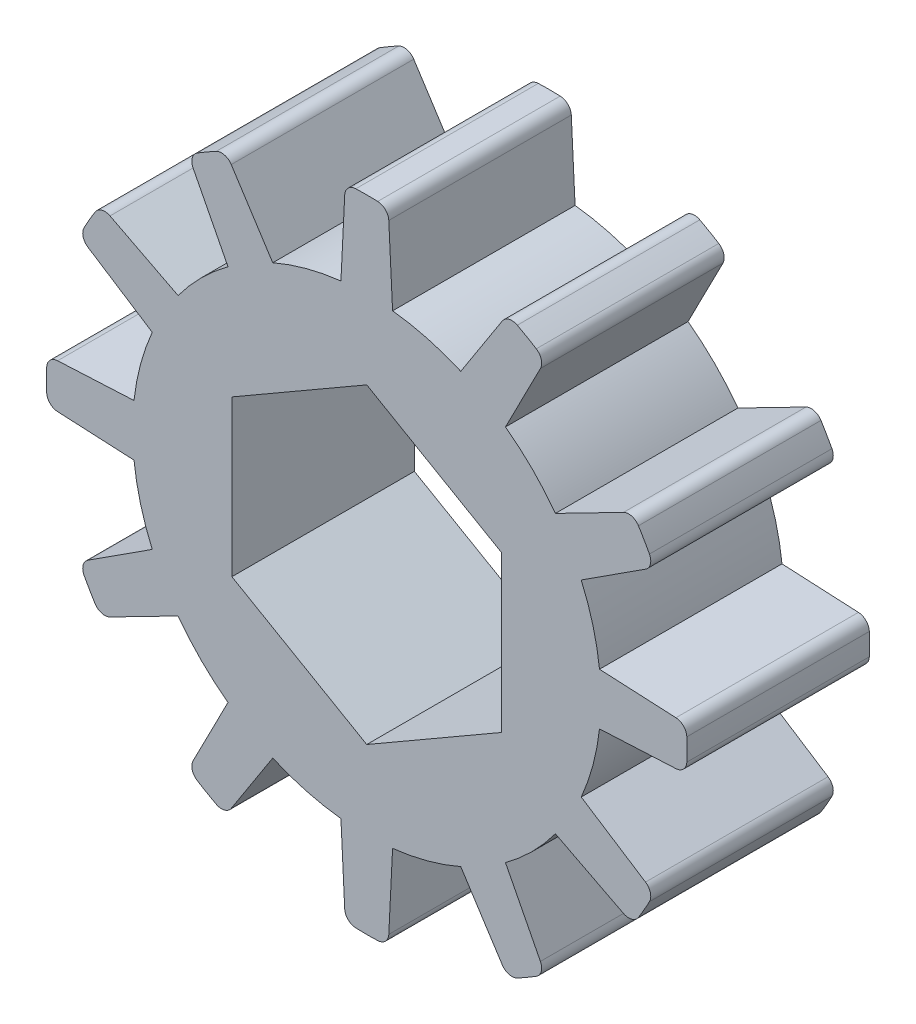
SolidWorks part; units mm, degrees
material "ABS"
ref_plane "Alzado" through (0, 0, 0) normal (0, 0, 1) x (1, 0, 0)
ref_plane "Planta" through (0, 0, 0) normal (0, 1, 0) x (1, 0, 0)
ref_plane "Vista lateral" through (0, 0, 0) normal (1, 0, 0) x (0, 0, -1)
sketch "Croquis1" plane through (0, 0, 0) normal (0, 0, 1) x (1, 0, 0)
  line L0 (0, 0) -> (0, 4.6049) construction
  line L1 (0.375, 5.5679) -> (0.45, 4.0556)
  line L2 (-0.375, 5.5679) -> (-0.45, 4.0556)
  line L3 (2.4592, 5.0094) -> (1.6381, 3.7373)
  line L4 (3.1087, 4.6344) -> (2.4175, 3.2873)
  line L5 (4.6344, 3.1087) -> (3.2873, 2.4175)
  line L6 (5.0094, 2.4592) -> (3.7373, 1.6381)
  line L7 (5.5679, 0.375) -> (4.0556, 0.45)
  line L8 (5.5679, -0.375) -> (4.0556, -0.45)
  line L9 (5.0094, -2.4592) -> (3.7373, -1.6381)
  line L10 (4.6344, -3.1087) -> (3.2873, -2.4175)
  line L11 (3.1087, -4.6344) -> (2.4175, -3.2873)
  line L12 (2.4592, -5.0094) -> (1.6381, -3.7373)
  line L13 (0.375, -5.5679) -> (0.45, -4.0556)
  line L14 (-0.375, -5.5679) -> (-0.45, -4.0556)
  line L15 (-2.4592, -5.0094) -> (-1.6381, -3.7373)
  line L16 (-3.1087, -4.6344) -> (-2.4175, -3.2873)
  line L17 (-4.6344, -3.1087) -> (-3.2873, -2.4175)
  line L18 (-5.0094, -2.4592) -> (-3.7373, -1.6381)
  line L19 (-5.5679, -0.375) -> (-4.0556, -0.45)
  line L20 (-5.5679, 0.375) -> (-4.0556, 0.45)
  line L21 (-5.0094, 2.4592) -> (-3.7373, 1.6381)
  line L22 (-4.6344, 3.1087) -> (-3.2873, 2.4175)
  line L23 (-3.1087, 4.6344) -> (-2.4175, 3.2873)
  line L24 (-2.4592, 5.0094) -> (-1.6381, 3.7373)
  circle A0 centre (0, 0) radius 0.5
  arc A1 (1.6381, 3.7373) -> (0.45, 4.0556) centre (0, 0) ccw
  arc A2 (3.1087, 4.6344) -> (2.4592, 5.0094) centre (0, 0) ccw
  arc A3 (5.0094, 2.4592) -> (4.6344, 3.1087) centre (0, 0) ccw
  arc A4 (5.5679, -0.375) -> (5.5679, 0.375) centre (0, 0) ccw
  arc A5 (4.6344, -3.1087) -> (5.0094, -2.4592) centre (0, 0) ccw
  arc A6 (2.4592, -5.0094) -> (3.1087, -4.6344) centre (0, 0) ccw
  arc A7 (-0.375, -5.5679) -> (0.375, -5.5679) centre (0, 0) ccw
  arc A8 (-3.1087, -4.6344) -> (-2.4592, -5.0094) centre (0, 0) ccw
  arc A9 (-5.0094, -2.4592) -> (-4.6344, -3.1087) centre (0, 0) ccw
  arc A10 (-5.5679, 0.375) -> (-5.5679, -0.375) centre (0, 0) ccw
  arc A11 (-4.6344, 3.1087) -> (-5.0094, 2.4592) centre (0, 0) ccw
  arc A12 (-2.4592, 5.0094) -> (-3.1087, 4.6344) centre (0, 0) ccw
  arc A13 (0.375, 5.5679) -> (-0.375, 5.5679) centre (0, 0) ccw
  arc A14 (3.2873, 2.4175) -> (2.4175, 3.2873) centre (0, 0) ccw
  arc A15 (4.0556, 0.45) -> (3.7373, 1.6381) centre (0, 0) ccw
  arc A16 (3.7373, -1.6381) -> (4.0556, -0.45) centre (0, 0) ccw
  arc A17 (2.4175, -3.2873) -> (3.2873, -2.4175) centre (0, 0) ccw
  arc A18 (0.45, -4.0556) -> (1.6381, -3.7373) centre (0, 0) ccw
  arc A19 (-1.6381, -3.7373) -> (-0.45, -4.0556) centre (0, 0) ccw
  arc A20 (-3.2873, -2.4175) -> (-2.4175, -3.2873) centre (0, 0) ccw
  arc A21 (-4.0556, -0.45) -> (-3.7373, -1.6381) centre (0, 0) ccw
  arc A22 (-3.7373, 1.6381) -> (-4.0556, 0.45) centre (0, 0) ccw
  arc A23 (-2.4175, 3.2873) -> (-3.2873, 2.4175) centre (0, 0) ccw
  arc A24 (-0.45, 4.0556) -> (-1.6381, 3.7373) centre (0, 0) ccw
  dimension "D1" = 0.9
  dimension "D2" = 1
  dimension "D4" = 1.5
  dimension "D3" = 0.75
  dimension "D6" = 1.23
  dimension "D5" = 12
extrude "Saliente-Extruir1" add sketch "Croquis1" along normal blind 3.18
sketch "Croquis10" plane through (0, 0, 0) normal (0, 0, -1) x (-1, 0, 0)
  line L1 (0, -2.7135) -> (2.35, -1.3568)
  line L2 (2.35, -1.3568) -> (2.35, 1.3568)
  line L3 (2.35, 1.3568) -> (0, 2.7135)
  line L4 (0, 2.7135) -> (-2.35, 1.3568)
  line L5 (-2.35, 1.3568) -> (-2.35, -1.3568)
  line L6 (-2.35, -1.3568) -> (0, -2.7135)
  circle A0 centre (0, 0) radius 2.35 construction
  dimension "D1" = 4.7
extrude "Cortar-Extruir3" cut sketch "Croquis10" against normal through all
fillet "Redondeo1" radius 0.2 24 edges at (5.5679, -0.375, 1.59) (-2.4592, -5.0094, 1.59) (-3.1087, -4.6344, 1.59) (0.375, -5.5679, 1.59) (-0.375, -5.5679, 1.59) (3.1087, -4.6344, 1.59) (2.4592, -5.0094, 1.59) (5.0094, -2.4592, 1.59) (4.6344, -3.1087, 1.59) (-4.6344, -3.1087, 1.59) (-5.0094, -2.4592, 1.59) (-5.5679, -0.375, 1.59) (-5.5679, 0.375, 1.59) (-5.0094, 2.4592, 1.59) (-4.6344, 3.1087, 1.59) (-3.1087, 4.6344, 1.59) (-2.4592, 5.0094, 1.59) (5.5679, 0.375, 1.59) (5.0094, 2.4592, 1.59) (4.6344, 3.1087, 1.59) (3.1087, 4.6344, 1.59) (2.4592, 5.0094, 1.59) (0.375, 5.5679, 1.59) (-0.375, 5.5679, 1.59)
